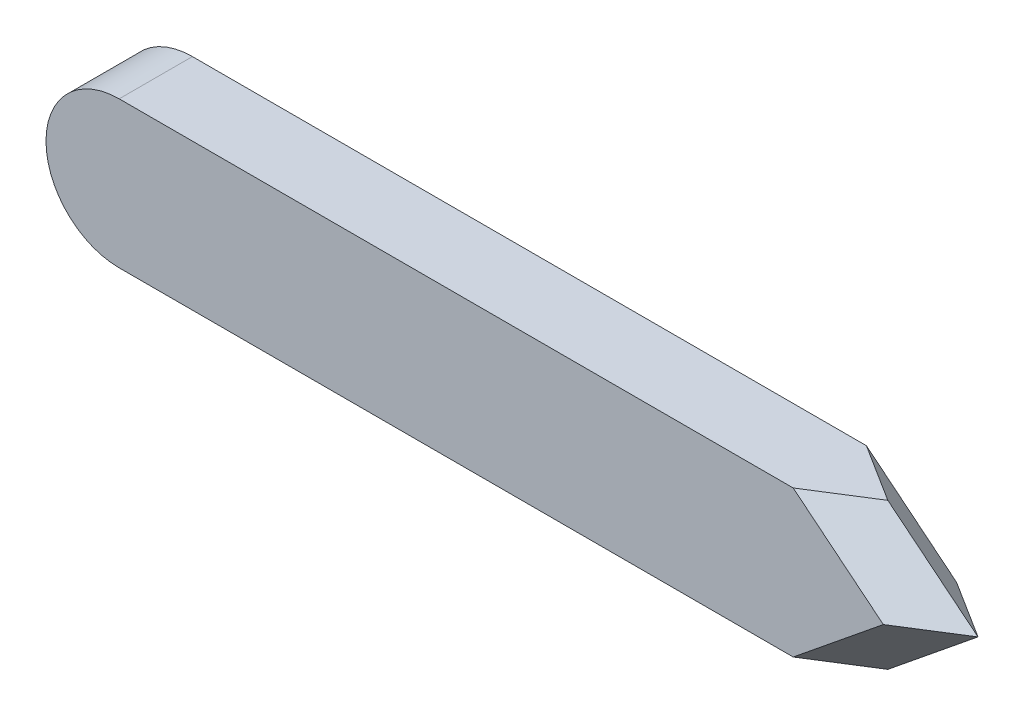
SolidWorks part; units mm, degrees
ref_plane "前视基准面" through (0, 0, 0) normal (0, 0, 1) x (1, 0, 0)
ref_plane "上视基准面" through (0, 0, 0) normal (0, 1, 0) x (1, 0, 0)
ref_plane "右视基准面" through (0, 0, 0) normal (1, 0, 0) x (0, 0, -1)
other "Configuration Table"
sketch "草图1" plane through (0, 0, 0) normal (0, 0, 1) x (1, 0, 0)
  line L0 (0, 0) -> (39.157, 0) construction
  line L2 (0, 4) -> (40, 4)
  line L3 (40, 4) -> (44.9261, 0)
  line L4 (40, -4) -> (44.9261, 0)
  line L5 (0, -4) -> (40, -4)
  arc A0 (0, 4) -> (0, -4) centre (0, 0) ccw
  dimension "D1" = 4
  dimension "D2" = 40
extrude "凸台-拉伸1" add sketch "草图1" along normal blind 4
sketch "草图2" plane through (0, 0, 0) normal (0, 0, -1) x (-1, 0, 0)
  circle A0 centre (0, 0) radius 2.6
  dimension "D1" = 5.2
extrude "切除-拉伸1" cut sketch "草图2" against normal blind 2.2
chamfer "倒角2" distance 2 angle 45 4 edges at (42.4631, -2, 0) (42.4631, 2, 0) (42.4631, -2, 4) (42.4631, 2, 4)
